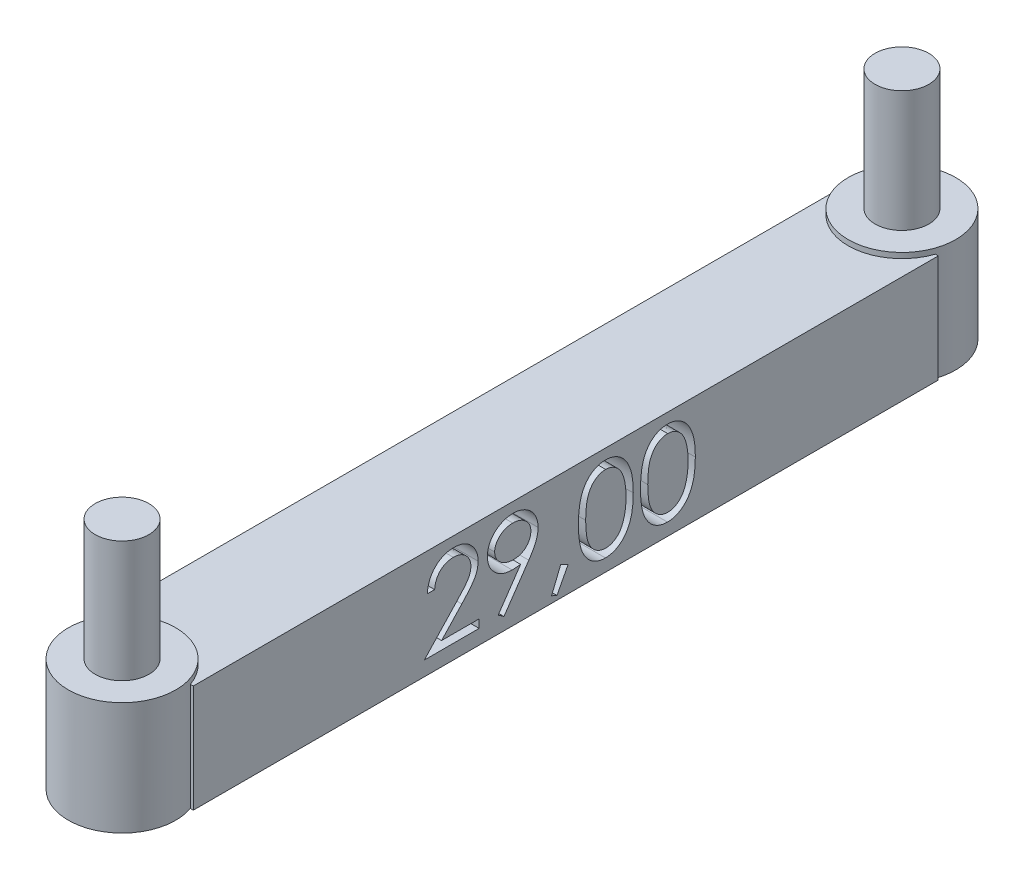
SolidWorks part; units mm, degrees
ref_plane "Ebene vorne" through (0, 0, 0) normal (0, 0, 1) x (1, 0, 0)
ref_plane "Ebene oben" through (0, 0, 0) normal (0, 1, 0) x (1, 0, 0)
ref_plane "Ebene rechts" through (0, 0, 0) normal (1, 0, 0) x (0, 0, -1)
sketch "Skizze1" plane through (0, 0, 0) normal (0, 0, 1) x (1, 0, 0)
  line L1 (-2, 2) -> (2, 2)
  line L2 (-2, 2) -> (-2, -2)
  line L3 (-2, -2) -> (2, -2)
  line L4 (2, 2) -> (2, -2)
  line L5 (-2, 2) -> (2, -2) construction
  line L6 (-2, -2) -> (2, 2) construction
  point P0 (0, 0)
  dimension "D1" = 4
  dimension "D2" = 4
extrude "Aufsatz-Linear austragen1" add sketch "Skizze1" along normal blind 27.7
sketch "Skizze2" plane through (0, 0, 0) normal (0, 1, 0) x (1, 0, 0)
  line L0 (0, -27.7) -> (0, 0) construction
  line L1 (2, -27.7) -> (-2, -27.7) construction
  circle A0 centre (0, -28.35) radius 2
  circle A2 centre (0, 0.65) radius 2
  point P9 (0, -13.85)
  dimension "D1" = 14.5
  dimension "D2" = 14.5
extrude "Aufsatz-Linear austragen2" add sketch "Skizze2" against normal blind 4 and the other way blind 0.2 from offset 2
sketch "Skizze3" plane through (0, 2.2, 0) normal (0, 1, 0) x (1, 0, 0)
  circle A0 centre (0, -28.35) radius 1
  circle A2 centre (0, 0.65) radius 1
extrude "Aufsatz-Linear austragen4" add sketch "Skizze3" along normal blind 4.5
fillet "Verrundung1" [suppressed] radius 2
sketch "Skizze4" plane through (2, 0, 0) normal (1, 0, 0) x (0, 0, -1)
  text T0 "29,00" font "Century Gothic" height 3
extrude "Schnitt-Linear austragen2" cut sketch "Skizze4" against normal blind 1
